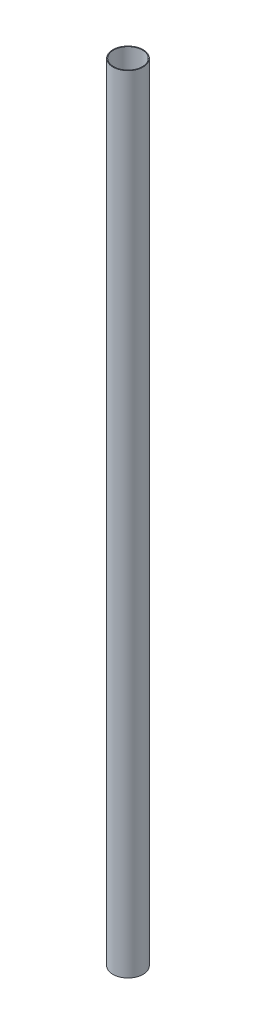
SolidWorks part; units mm, degrees
material "6063-T6"
ref_plane "Front Plane" through (0, 0, 0) normal (0, 0, 1) x (1, 0, 0)
ref_plane "Top Plane" through (0, 0, 0) normal (0, 1, 0) x (1, 0, 0)
ref_plane "Right Plane" through (0, 0, 0) normal (1, 0, 0) x (0, 0, -1)
sketch "Sketch1" plane through (0, 0, 0) normal (0, 1, 0) x (1, 0, 0)
  circle A0 centre (0, 0) radius 24.1554
  circle A1 centre (0, 0) radius 25.4
  dimension "D1" = 50.8
  dimension "D2" = 1.2446
extrude "body" add sketch "Sketch1" along normal blind 1320.8
